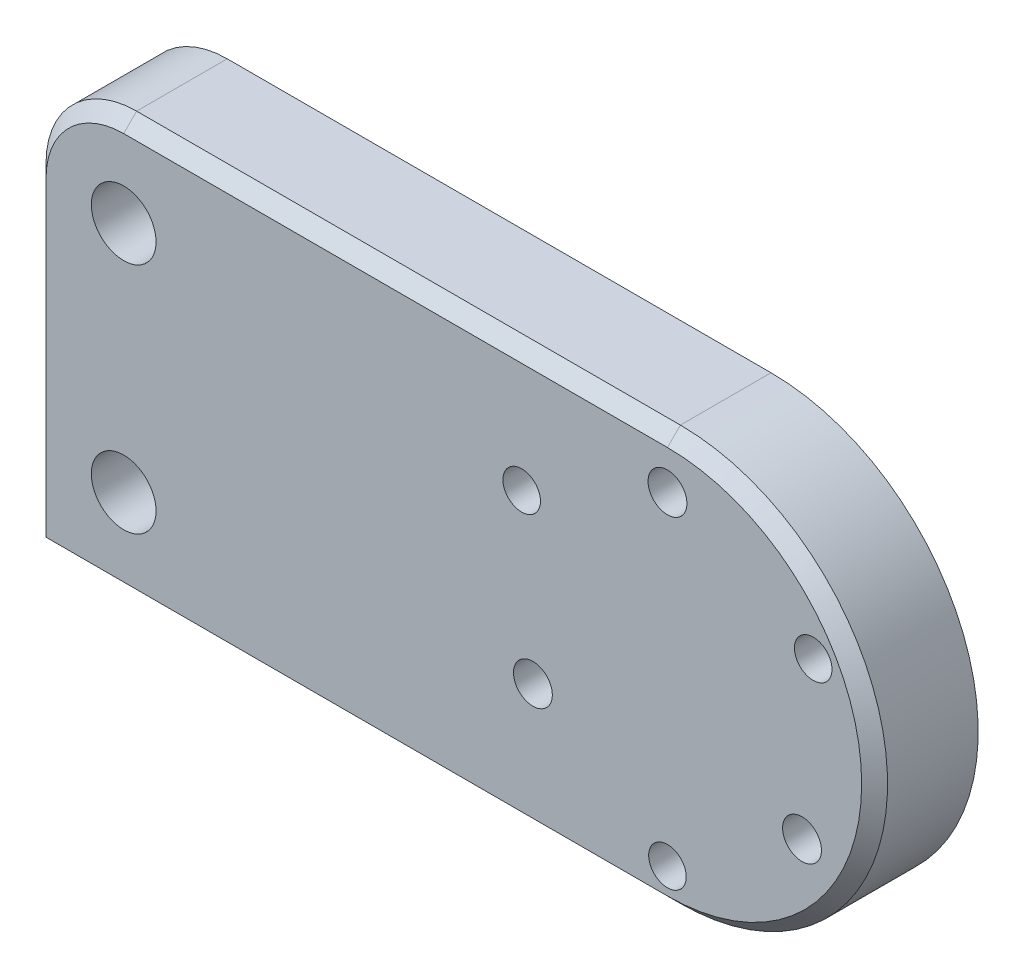
SolidWorks part; units mm, degrees
ref_plane "前视基准面" through (0, 0, 0) normal (0, 0, 1) x (1, 0, 0)
ref_plane "上视基准面" through (0, 0, 0) normal (0, 1, 0) x (1, 0, 0)
ref_plane "右视基准面" through (0, 0, 0) normal (1, 0, 0) x (0, 0, -1)
sketch "草图1" plane through (0, 0, 0) normal (0, 0, 1) x (1, 0, 0)
  line L0 (0, 16) -> (-42, 16)
  line L1 (0, -16) -> (-49, -16)
  line L2 (-49, 9) -> (-49, -16)
  line L3 (-42, 9) -> (-42, -9) construction
  line L4 (-42, 0) -> (0, 0) construction
  line L5 (-35, 16) -> (-35, -16) construction
  circle A0 centre (0, -13) radius 1.45 construction
  circle A1 centre (10.3923, -6) radius 1.5 construction
  circle A2 centre (11.2583, 6.5) radius 1.45 construction
  circle A3 centre (-10.3923, -6) radius 1.5 construction
  circle A4 centre (-11.2583, 6.5) radius 1.45 construction
  circle A5 centre (0, 12) radius 1.5 construction
  circle A6 centre (0, -13) radius 1.45
  circle A7 centre (10.3923, -6) radius 1.5
  circle A8 centre (11.2583, 6.5) radius 1.45
  circle A9 centre (-10.3923, -6) radius 1.5
  circle A10 centre (-11.2583, 6.5) radius 1.45
  circle A11 centre (0, 12) radius 1.5
  circle A12 centre (0, 0) radius 16 construction
  circle A13 centre (0, 0) radius 16 construction
  arc A14 (0, 16) -> (0, -16) centre (0, 0) cw
  circle A15 centre (-42, 9) radius 2.5
  circle A16 centre (-42, -9) radius 2.5
  arc A17 (-42, 16) -> (-49, 9) centre (-42, 9) ccw
  dimension "D2" = 5
  dimension "D6" = 7
  dimension "D1" = 18
  dimension "D3" = 7
  dimension "D4" = 7
  dimension "D5" = 42
extrude "凸台-拉伸1" add sketch "草图1" along normal blind 8
chamfer "倒角1" distance 1 angle 45 1 edges at (-49, -16, 4)
chamfer "倒角2" distance 1 angle 45 5 edges at (-24, -16, 8) (-49, -3, 8) (16, 0, 8) (-46.9497, 13.9497, 8) (-21, 16, 8)
